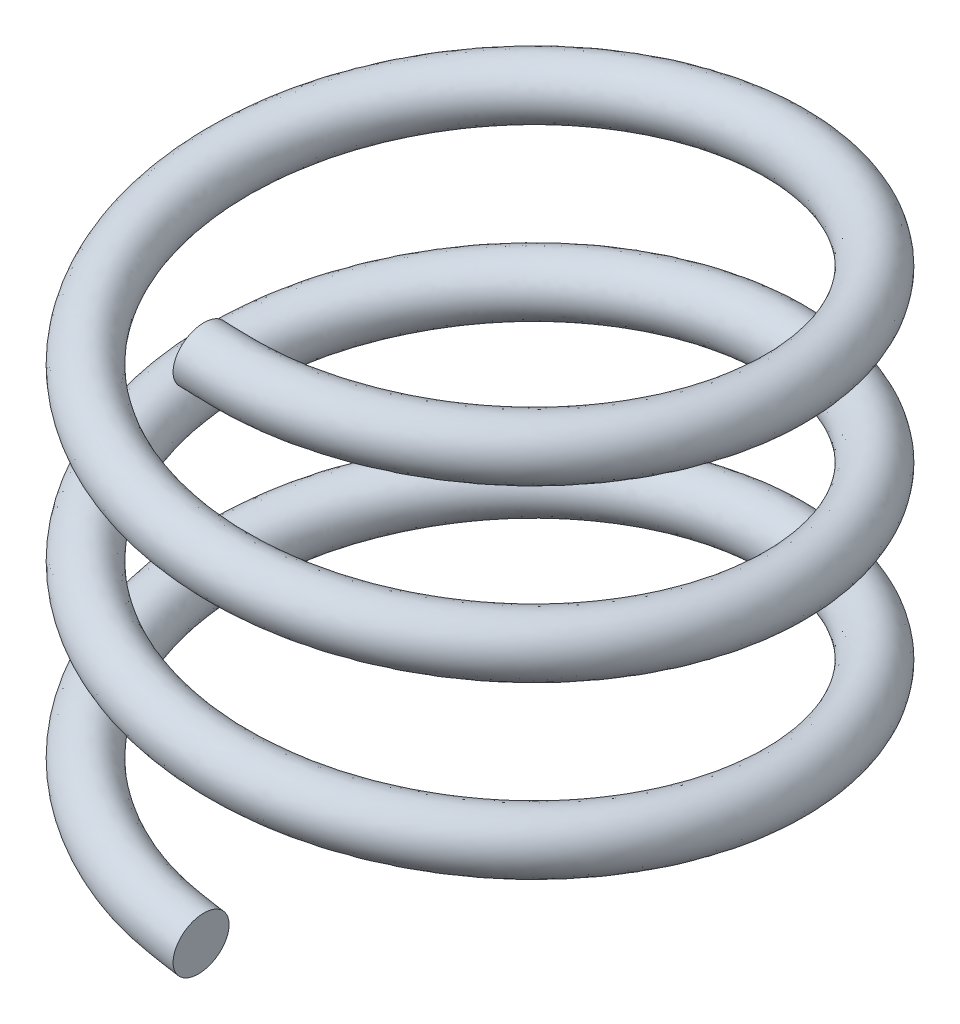
SolidWorks part; units mm, degrees
ref_plane "Plane1" through (0, 0, 0) normal (0, 0, 1) x (1, 0, 0)
ref_plane "Plane2" through (0, 0, 0) normal (0, 1, 0) x (1, 0, 0)
ref_plane "Plane3" through (0, 0, 0) normal (1, 0, 0) x (0, 0, -1)
sketch "Sketch1" plane through (0, 0, 0) normal (0, 1, 0) x (1, 0, 0)
  circle A0 centre (0, 0) radius 3.81
  dimension "D1" = 7.62
curve "Helix1" pitch 2.3283 height 6.985 radius 3.81 left hand yes centre (0, 0, 0) axis (0, 1, 0) start towards (0, 0, 1)
ref_plane "Plane4" through (0, 0, 3.81) normal (-0.9953, 0.0968, 0) x (0, 0, 1)
sketch "Sketch2" plane through (0, 0, 3.81) normal (-0.9953, 0.0968, 0) x (0, 0, 1)
  circle A0 centre (0.0002, -0.0006) radius 0.381
  dimension "D1" = 0.762
sweep "Base-Sweep" add profiles "Sketch2" path "Helix1"
ref_axis "Axis1" through (0, 50, 0) along (0, -1, 0)
